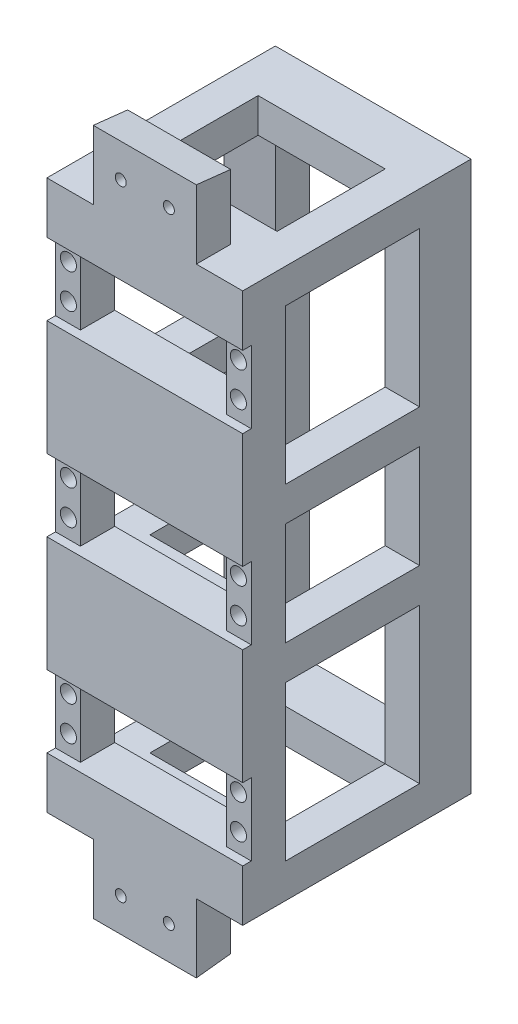
SolidWorks part; units mm, degrees
other "Markup1"
sketch "Sketch14" plane through (-28.5, -100, 33.25) normal (-0.1152, -0.4489, 0.8861) x (0.8144, -0.5535, -0.1745)
sketch "Sketch15" plane through (-28.5, -100, 33.25) normal (-0.1152, -0.4489, 0.8861) x (0.8144, -0.5535, -0.1745)
sketch "Sketch16" plane through (-28.5, -100, 33.25) normal (-0.1152, -0.4489, 0.8861) x (0.8144, -0.5535, -0.1745)
sketch "Sketch17" plane through (-28.5, -100, 33.25) normal (-0.1152, -0.4489, 0.8861) x (0.8144, -0.5535, -0.1745)
sketch "Sketch18" plane through (-28.5, -100, 33.25) normal (-0.1152, -0.4489, 0.8861) x (0.8144, -0.5535, -0.1745)
sketch "Sketch19" plane through (-28.5, -100, 33.25) normal (-0.1152, -0.4489, 0.8861) x (0.8144, -0.5535, -0.1745)
sketch "Sketch20" plane through (-28.5, -100, 33.25) normal (-0.1152, -0.4489, 0.8861) x (0.8144, -0.5535, -0.1745)
sketch "Sketch21" plane through (-28.5, -100, 33.25) normal (-0.1152, -0.4489, 0.8861) x (0.8144, -0.5535, -0.1745)
sketch "Sketch22" plane through (-28.5, -100, 33.25) normal (-0.1152, -0.4489, 0.8861) x (0.8144, -0.5535, -0.1745)
sketch "Sketch23" plane through (-28.5, -100, 33.25) normal (-0.1152, -0.4489, 0.8861) x (0.8144, -0.5535, -0.1745)
sketch "Sketch24" plane through (-28.5, -100, 33.25) normal (-0.1152, -0.4489, 0.8861) x (0.8144, -0.5535, -0.1745)
sketch "Sketch25" plane through (-28.5, -100, 33.25) normal (-0.1152, -0.4489, 0.8861) x (0.8144, -0.5535, -0.1745)
sketch "Sketch26" plane through (-28.5, -100, 33.25) normal (-0.1152, -0.4489, 0.8861) x (0.8144, -0.5535, -0.1745)
sketch "Sketch27" plane through (-28.5, -100, 33.25) normal (-0.1152, -0.4489, 0.8861) x (0.8144, -0.5535, -0.1745)
sketch "Sketch28" plane through (-28.5, -100, 33.25) normal (-0.1152, -0.4489, 0.8861) x (0.8144, -0.5535, -0.1745)
sketch "Sketch29" plane through (-28.5, -100, 33.25) normal (-0.1152, -0.4489, 0.8861) x (0.8144, -0.5535, -0.1745)
sketch "Sketch30" plane through (-28.5, -100, 33.25) normal (-0.1152, -0.4489, 0.8861) x (0.8144, -0.5535, -0.1745)
sketch "Sketch31" plane through (-28.5, -100, 33.25) normal (-0.1152, -0.4489, 0.8861) x (0.8144, -0.5535, -0.1745)
sketch "Sketch32" plane through (-28.5, -100, 33.25) normal (-0.1152, -0.4489, 0.8861) x (0.8144, -0.5535, -0.1745)
sketch "Sketch33" plane through (-28.5, -100, 33.25) normal (-0.1152, -0.4489, 0.8861) x (0.8144, -0.5535, -0.1745)
sketch "Sketch34" plane through (-28.5, -100, 33.25) normal (-0.1152, -0.4489, 0.8861) x (0.8144, -0.5535, -0.1745)
sketch "Sketch35" plane through (-28.5, -100, 33.25) normal (-0.1152, -0.4489, 0.8861) x (0.8144, -0.5535, -0.1745)
sketch "Sketch36" plane through (-28.5, -100, 33.25) normal (-0.1152, -0.4489, 0.8861) x (0.8144, -0.5535, -0.1745)
sketch "Sketch38" plane through (-28.5, -100, 33.25) normal (-0.1152, -0.4489, 0.8861) x (0.8144, -0.5535, -0.1745)
sketch "Sketch39" plane through (-28.5, -100, 33.25) normal (-0.1152, -0.4489, 0.8861) x (0.8144, -0.5535, -0.1745)
sketch "Sketch40" plane through (-28.5, -100, 33.25) normal (-0.1152, -0.4489, 0.8861) x (0.8144, -0.5535, -0.1745)
sketch "Sketch41" plane through (-28.5, -100, 33.25) normal (-0.1152, -0.4489, 0.8861) x (0.8144, -0.5535, -0.1745)
sketch "Sketch42" plane through (-28.5, -100, 33.25) normal (-0.1152, -0.4489, 0.8861) x (0.8144, -0.5535, -0.1745)
material "PLA"
ref_plane "Plan de face" through (0, 0, 0) normal (0, 0, 1) x (1, 0, 0)
ref_plane "Plan de dessus" through (0, 0, 0) normal (0, 1, 0) x (1, 0, 0)
ref_plane "Plan de droite" through (0, 0, 0) normal (1, 0, 0) x (0, 0, -1)
sketch "Sketch1" plane through (0, 0, 0) normal (0, 0, 1) x (1, 0, 0)
  line L1 (-28.5, -80) -> (28.5, -80)
  line L2 (-28.5, -80) -> (-28.5, 80)
  line L3 (-28.5, 80) -> (28.5, 80)
  line L4 (28.5, -80) -> (28.5, 80)
  line L5 (-28.5, -80) -> (28.5, 80) construction
  line L6 (-28.5, 80) -> (28.5, -80) construction
  point P0 (0, 0)
  dimension "D1" = 57
  dimension "D2" = 160
extrude "Boss-Extrude1" add sketch "Sketch1" along normal mid plane 66.5
sketch "Sketch2" plane through (0, 0, 33.25) normal (0, 0, 1) x (1, 0, 0)
  line L0 (-21.25, 65) -> (21.25, 65)
  line L14 (-21.25, 44) -> (-21.25, 65)
  line L15 (-21.25, -10.5) -> (21.25, -10.5)
  line L23 (-21.25, -10.5) -> (-21.25, 10.5)
  line L24 (-21.25, 10.5) -> (21.25, 10.5)
  line L25 (21.25, -10.5) -> (21.25, 10.5)
  line L26 (-21.25, -10.5) -> (21.25, 10.5) construction
  line L27 (-21.25, 10.5) -> (21.25, -10.5) construction
  line L32 (-21.25, 44) -> (21.25, 44)
  line L34 (21.25, 44) -> (21.25, 65)
  line L37 (31.35, 0) -> (-31.35, 0) construction
  line L38 (21.25, -44) -> (21.25, -65)
  line L39 (-21.25, -44) -> (21.25, -44)
  line L40 (-21.25, -44) -> (-21.25, -65)
  line L41 (-21.25, -65) -> (21.25, -65)
  line L43 (28.5, 80) -> (-28.5, 80) construction
  point P0 (0, 0)
  dimension "D1" = 21
  dimension "D2" = 42.5
  dimension "D3" = 2
  dimension "D4" = 15
extrude "Cut-Extrude1" cut sketch "Sketch2" against normal offset from surface (51.5 mm away) 15 up to face at (0, 0, -33.25)
sketch "Sketch3" plane through (-28.5, 0, 0) normal (-1, 0, 0) x (0, 0, 1)
  line L0 (-33.25, 80) -> (-33.25, -80) construction
  line L1 (31.35, 0) -> (-31.35, 0) construction
  line L2 (13.25, -70) -> (-18.25, -70)
  line L3 (13.25, -70) -> (13.25, -25)
  line L4 (13.25, -25) -> (-18.25, -25)
  line L5 (-18.25, -70) -> (-18.25, -25)
  line L6 (-18.25, -15) -> (13.25, -15)
  line L7 (33.25, 80) -> (33.25, -80) construction
  line L9 (33.25, -80) -> (-33.25, -80) construction
  line L15 (-18.25, -15) -> (-18.25, 15)
  line L16 (-18.25, 15) -> (13.25, 15)
  line L17 (13.25, -15) -> (13.25, 15)
  line L18 (-18.25, 70) -> (-18.25, 25)
  line L19 (13.25, 25) -> (-18.25, 25)
  line L20 (13.25, 70) -> (13.25, 25)
  line L21 (13.25, 70) -> (-18.25, 70)
  point P14 (13.25, 0)
  dimension "D1" = 15
  dimension "D2" = 20
  dimension "D3" = 45
  dimension "D4" = 10
  dimension "D5" = 10
extrude "Cut-Extrude2" cut sketch "Sketch3" against normal through all
sketch "Sketch4" plane through (0, 0, -18.25) normal (0, 0, 1) x (1, 0, 0)
  line L1 (18.5, 70) -> (-18.5, 70)
  line L2 (18.5, 70) -> (18.5, -70)
  line L3 (18.5, -70) -> (-18.5, -70)
  line L4 (-18.5, 70) -> (-18.5, -70)
  line L5 (-28.5, -25) -> (-28.5, -70) construction
  line L6 (28.5, -25) -> (28.5, -70) construction
  line L7 (28.5, 80) -> (-28.5, 80) construction
  line L8 (-28.5, -80) -> (28.5, -80) construction
  dimension "D1" = 10
  dimension "D2" = 10
  dimension "D3" = 10
  dimension "D4" = 10
extrude "Cut-Extrude3" cut sketch "Sketch4" against normal through all
sketch "Sketch5" plane through (0, 0, 33.25) normal (0, 0, 1) x (1, 0, 0)
  line L0 (28.5, -80) -> (28.5, 80) construction
  line L5 (-21.25, -10.5) -> (21.25, -10.5) construction
  line L6 (-28.5, -10.5) -> (28.5, -10.5)
  line L7 (-28.5, 44) -> (28.5, 44)
  line L12 (-28.5, 44) -> (-28.5, 65)
  line L17 (-28.5, -10.5) -> (-28.5, 10.5)
  line L18 (-28.5, 10.5) -> (28.5, 10.5)
  line L19 (28.5, -10.5) -> (28.5, 10.5)
  line L20 (-28.5, -10.5) -> (28.5, 10.5) construction
  line L21 (-28.5, 10.5) -> (28.5, -10.5) construction
  line L22 (-28.5, 65) -> (28.5, 65)
  line L23 (28.5, 44) -> (28.5, 65)
  line L24 (-28.5, 44) -> (28.5, 65) construction
  line L25 (-28.5, 65) -> (28.5, 44) construction
  line L26 (21.25, 65) -> (-21.25, 65) construction
  line L27 (31.35, 0) -> (-31.35, 0) construction
  line L28 (-28.5, -65) -> (28.5, -44) construction
  line L29 (-28.5, -44) -> (28.5, -65) construction
  line L30 (28.5, -44) -> (28.5, -65)
  line L31 (-28.5, -65) -> (28.5, -65)
  line L32 (-28.5, -44) -> (-28.5, -65)
  line L33 (-28.5, -44) -> (28.5, -44)
  point P0 (0, 0)
  point P10 (0, 54.5)
  point P23 (0, -54.5)
  dimension "D1" = 2
extrude "Cut-Extrude4" cut sketch "Sketch5" against normal blind 2.5
sketch "Sketch37" plane through (-28.5, 0, 0) normal (-1, 0, 0) x (0, 0, 1)
  line L0 (-18.25, 25) -> (13.25, 25) construction
  line L1 (-18.25, 70) -> (20.75, 70)
  line L2 (-18.25, 70) -> (-18.25, 25)
  line L3 (-18.25, 25) -> (20.75, 25)
  line L4 (20.75, 70) -> (20.75, 25)
  line L5 (30.75, 65) -> (30.75, 44) construction
  line L6 (-18.25, -15) -> (13.25, -15) construction
  line L7 (-18.25, 15) -> (20.75, 15)
  line L8 (-18.25, 15) -> (-18.25, -15)
  line L9 (-18.25, -15) -> (20.75, -15)
  line L10 (20.75, 15) -> (20.75, -15)
  line L11 (-18.25, -25) -> (20.75, -25)
  line L12 (-18.25, -25) -> (-18.25, -70)
  line L13 (-18.25, -70) -> (20.75, -70)
  line L14 (20.75, -25) -> (20.75, -70)
  line L15 (-18.25, -70) -> (13.25, -70) construction
  dimension "D1" = 10
extrude "Cut-Extrude10" cut sketch "Sketch37" against normal through all
sketch "Sketch6" plane through (0, 0, 30.75) normal (0, 0, 1) x (1, 0, 0)
  line L0 (24.75, 5) -> (24.75, 59.5) construction
  line L2 (0, -36.575) -> (0, 36.575) construction
  line L3 (31.35, 0) -> (-31.35, 0) construction
  line L4 (28.5, 10.5) -> (-28.5, 10.5) construction
  circle A4 centre (24.75, 5) radius 2.35
  circle A5 centre (-24.75, 5) radius 2.35
  circle A6 centre (-24.75, -5) radius 2.35
  circle A7 centre (24.75, -5) radius 2.35
  circle A28 centre (24.75, 59.5) radius 2.35
  circle A29 centre (-24.75, 59.5) radius 2.35
  circle A30 centre (-24.75, 49.5) radius 2.35
  circle A31 centre (24.75, 49.5) radius 2.35
  circle A32 centre (24.75, -49.5) radius 2.35
  circle A33 centre (-24.75, -49.5) radius 2.35
  circle A34 centre (-24.75, -59.5) radius 2.35
  circle A35 centre (24.75, -59.5) radius 2.35
  point P2 (0, 10.5)
  point P50 (0, -10.5)
  dimension "D2" = 4.7
  dimension "D1" = 24.75
  dimension "D3" = 54.5
  dimension "D5" = 5
extrude "Cut-Extrude6" cut sketch "Sketch6" against normal up to next
sketch "Sketch8" plane through (0, 80, 0) normal (0, 1, 0) x (1, 0, 0)
  line L1 (-18.5, 18.25) -> (18.5, 18.25)
  line L2 (-18.5, 18.25) -> (-18.5, -13.25)
  line L3 (-18.5, -13.25) -> (18.5, -13.25)
  line L4 (18.5, 18.25) -> (18.5, -13.25)
  line L6 (-18.5, 18.25) -> (-28.5, 18.25) construction
  line L7 (-18.5, 33.25) -> (-18.5, 18.25) construction
  line L10 (18.5, 33.25) -> (18.5, 18.25) construction
  line L11 (28.5, -33.25) -> (-28.5, -33.25) construction
  dimension "D1" = 20
extrude "Cut-Extrude7" cut sketch "Sketch8" against normal through all
sketch "Sketch11" plane through (0, -80, 0) normal (0, -1, 0) x (1, 0, 0)
  line L0 (-28.5, 33.25) -> (28.5, 33.25) construction
  line L1 (-15, 23.25) -> (15, 23.25)
  line L2 (-15, 23.25) -> (-15, 33.25)
  line L3 (-15, 33.25) -> (15, 33.25)
  line L4 (15, 23.25) -> (15, 33.25)
  line L5 (-15, 23.25) -> (15, 33.25) construction
  line L6 (-15, 33.25) -> (15, 23.25) construction
  point P0 (0, 28.25)
  point P5 (0, 33.25)
  dimension "D1" = 10
  dimension "D2" = 30
extrude "Boss-Extrude3" add sketch "Sketch11" along normal up to surface (18.8889 mm away)
sketch "Sketch13" plane through (0, 80, 0) normal (0, 1, 0) x (1, 0, 0)
  line L4 (15, -23.25) -> (-15, -23.25)
  line L5 (15, -33.25) -> (15, -23.25)
  line L6 (-15, -33.25) -> (15, -33.25)
  line L7 (-15, -23.25) -> (-15, -33.25)
  line L8 (15, -23.25) -> (-15, -23.25)
  line L9 (15, -33.25) -> (15, -23.25)
  line L10 (-15, -33.25) -> (15, -33.25)
  line L11 (-15, -23.25) -> (-15, -33.25)
  dimension "D1" = 0
extrude "Boss-Extrude4" add sketch "Sketch13" along normal up to surface (18.8889 mm away)
sketch "Sketch12" plane through (0, 0, 33.25) normal (0, 0, 1) x (1, 0, 0)
  line L1 (31.35, 0) -> (-31.35, 0) construction
  circle A3 centre (7, 90.25) radius 2.1
  circle A4 centre (7, 90.25) radius 2.1 construction
  circle A5 centre (7, -90.25) radius 2.1
  circle A6 centre (7, -90.25) radius 2.1 construction
  circle A7 centre (7, -90.25) radius 1.6
  circle A8 centre (7, 90.25) radius 1.6
  circle A9 centre (-7, -90.25) radius 1.6
  circle A10 centre (-7, 90.25) radius 2.1
  circle A11 centre (-7, 90.25) radius 2.1 construction
  circle A12 centre (-7, -90.25) radius 2.1
  circle A13 centre (-7, -90.25) radius 2.1 construction
  circle A14 centre (-7, 90.25) radius 1.6
  dimension "D1" = 0
  dimension "D3" = 3.2
  dimension "D2" = 0
  dimension "D4" = 0
  dimension "D5" = 0
extrude "Cut-Extrude9" cut sketch "Sketch12" against normal up to next
chamfer "Chamfer1" distance 10 distance2 5 9 edges at (-23.5, 25, -18.25) (-23.5, 70, -18.25) (-23.5, -70, -18.25) (-23.5, -25, -18.25) (-23.5, -15, -18.25) (-23.5, 15, -18.25) (-18.5, 47.5, -18.25) (-18.5, -47.5, -18.25) (-18.5, 0, -18.25)
